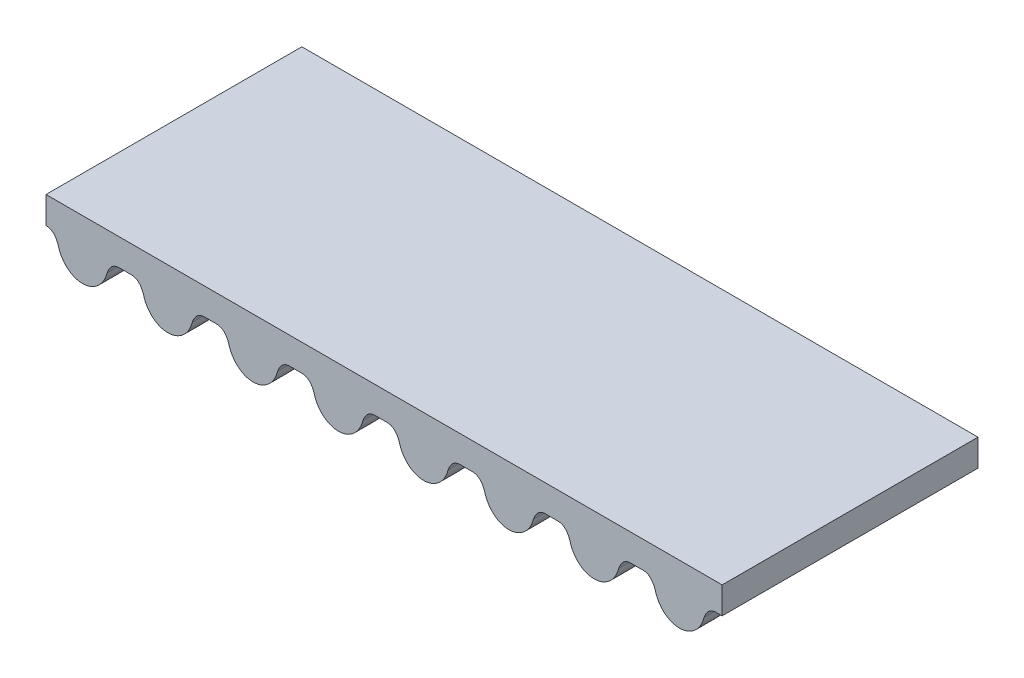
SolidWorks part; units mm, degrees
ref_plane "Front Plane" through (0, 0, 0) normal (0, 0, 1) x (1, 0, 0)
ref_plane "Top Plane" through (0, 0, 0) normal (0, 1, 0) x (1, 0, 0)
ref_plane "Right Plane" through (0, 0, 0) normal (1, 0, 0) x (0, 0, -1)
sketch "Sketch1" plane through (0, 0, 0) normal (0, 0, 1) x (1, 0, 0)
  line L0 (0, 0.75) -> (0, 0) construction
  line L1 (0.8572, 0) -> (0, 0) construction
  line L2 (0, 0.75) -> (0, 1.3798)
  line L12 (3.8572, 1.3798) -> (0, 1.3798)
  line L15 (1.7144, 0.75) -> (1.8572, 0.75)
  line L16 (1.8572, 0.75) -> (2, 0.75)
  line L17 (3.7144, 0.75) -> (3.8572, 0.75)
  line L18 (3.8572, 0.75) -> (4, 0.75)
  line L19 (5.7144, 0.75) -> (5.8572, 0.75)
  line L20 (5.8572, 0.75) -> (6, 0.75)
  line L21 (7.7144, 0.75) -> (7.8572, 0.75)
  line L22 (7.8572, 0.75) -> (8, 0.75)
  line L23 (9.7144, 0.75) -> (9.8572, 0.75)
  line L24 (9.8572, 0.75) -> (10, 0.75)
  line L25 (11.7144, 0.75) -> (11.8572, 0.75)
  line L26 (11.8572, 0.75) -> (12, 0.75)
  line L27 (13.7144, 0.75) -> (13.8572, 0.75)
  line L28 (13.8572, 0.75) -> (14, 0.75)
  line L29 (15.7144, 0.75) -> (15.8572, 0.75)
  line L30 (15.8572, 0.75) -> (15.8572, 1.3798)
  line L31 (15.8572, 1.3798) -> (11.8572, 1.3798)
  line L32 (11.8572, 1.3798) -> (7.8572, 1.3798)
  line L33 (7.8572, 1.3798) -> (3.8572, 1.3798)
  spline S16 degree 2 poles (0, 0.75) (0.1946, 0.75) (0.2844, 0.4991) knots 0.054545 0.054545 0.054545 0.072727 0.072727 0.072727
  spline S17 degree 3 poles (0.2844, 0.4991) (0.355, 0.2112) (0.5844, 0) (0.8572, 0) knots 0.072727 0.072727 0.072727 0.072727 0.090909 0.090909 0.090909 0.090909
  spline S18 degree 3 poles (0.8572, 0) (1.13, 0) (1.3594, 0.2112) (1.43, 0.4991) knots 0.090909 0.090909 0.090909 0.090909 0.109091 0.109091 0.109091 0.109091
  spline S19 degree 2 poles (1.43, 0.4991) (1.5198, 0.75) (1.7144, 0.75) knots 0.109091 0.109091 0.109091 0.127273 0.127273 0.127273
  spline S20 degree 2 poles (2, 0.75) (2.1946, 0.75) (2.2844, 0.4991) knots 0.163636 0.163636 0.163636 0.181818 0.181818 0.181818
  spline S21 degree 3 poles (2.2844, 0.4991) (2.355, 0.2112) (2.5844, 0) (2.8572, 0) knots 0.181818 0.181818 0.181818 0.181818 0.2 0.2 0.2 0.2
  spline S22 degree 3 poles (2.8572, 0) (3.13, 0) (3.3594, 0.2112) (3.43, 0.4991) knots 0.2 0.2 0.2 0.2 0.218182 0.218182 0.218182 0.218182
  spline S23 degree 2 poles (3.43, 0.4991) (3.5198, 0.75) (3.7144, 0.75) knots 0.218182 0.218182 0.218182 0.236364 0.236364 0.236364
  spline S24 degree 2 poles (4, 0.75) (4.1946, 0.75) (4.2844, 0.4991) knots 0.272727 0.272727 0.272727 0.290909 0.290909 0.290909
  spline S25 degree 3 poles (4.2844, 0.4991) (4.355, 0.2112) (4.5844, 0) (4.8572, 0) knots 0.290909 0.290909 0.290909 0.290909 0.309091 0.309091 0.309091 0.309091
  spline S26 degree 3 poles (4.8572, 0) (5.13, 0) (5.3594, 0.2112) (5.43, 0.4991) knots 0.309091 0.309091 0.309091 0.309091 0.327273 0.327273 0.327273 0.327273
  spline S27 degree 2 poles (5.43, 0.4991) (5.5198, 0.75) (5.7144, 0.75) knots 0.327273 0.327273 0.327273 0.345455 0.345455 0.345455
  spline S28 degree 2 poles (6, 0.75) (6.1946, 0.75) (6.2844, 0.4991) knots 0.381818 0.381818 0.381818 0.4 0.4 0.4
  spline S29 degree 3 poles (6.2844, 0.4991) (6.355, 0.2112) (6.5844, 0) (6.8572, 0) knots 0.4 0.4 0.4 0.4 0.418182 0.418182 0.418182 0.418182
  spline S30 degree 3 poles (6.8572, 0) (7.13, 0) (7.3594, 0.2112) (7.43, 0.4991) knots 0.418182 0.418182 0.418182 0.418182 0.436364 0.436364 0.436364 0.436364
  spline S31 degree 2 poles (7.43, 0.4991) (7.5198, 0.75) (7.7144, 0.75) knots 0.436364 0.436364 0.436364 0.454545 0.454545 0.454545
  spline S32 degree 2 poles (8, 0.75) (8.1946, 0.75) (8.2844, 0.4991) knots 0.490909 0.490909 0.490909 0.509091 0.509091 0.509091
  spline S33 degree 3 poles (8.2844, 0.4991) (8.355, 0.2112) (8.5844, 0) (8.8572, 0) knots 0.509091 0.509091 0.509091 0.509091 0.527273 0.527273 0.527273 0.527273
  spline S34 degree 3 poles (8.8572, 0) (9.13, 0) (9.3594, 0.2112) (9.43, 0.4991) knots 0.527273 0.527273 0.527273 0.527273 0.545455 0.545455 0.545455 0.545455
  spline S35 degree 2 poles (9.43, 0.4991) (9.5198, 0.75) (9.7144, 0.75) knots 0.545455 0.545455 0.545455 0.563636 0.563636 0.563636
  spline S36 degree 2 poles (10, 0.75) (10.1946, 0.75) (10.2844, 0.4991) knots 0.6 0.6 0.6 0.618182 0.618182 0.618182
  spline S37 degree 3 poles (10.2844, 0.4991) (10.355, 0.2112) (10.5844, 0) (10.8572, 0) knots 0.618182 0.618182 0.618182 0.618182 0.636364 0.636364 0.636364 0.636364
  spline S38 degree 3 poles (10.8572, 0) (11.13, 0) (11.3594, 0.2112) (11.43, 0.4991) knots 0.636364 0.636364 0.636364 0.636364 0.654545 0.654545 0.654545 0.654545
  spline S39 degree 2 poles (11.43, 0.4991) (11.5198, 0.75) (11.7144, 0.75) knots 0.654545 0.654545 0.654545 0.672727 0.672727 0.672727
  spline S40 degree 2 poles (12, 0.75) (12.1946, 0.75) (12.2844, 0.4991) knots 0.709091 0.709091 0.709091 0.727273 0.727273 0.727273
  spline S41 degree 3 poles (12.2844, 0.4991) (12.355, 0.2112) (12.5844, 0) (12.8572, 0) knots 0.727273 0.727273 0.727273 0.727273 0.745455 0.745455 0.745455 0.745455
  spline S42 degree 3 poles (12.8572, 0) (13.13, 0) (13.3594, 0.2112) (13.43, 0.4991) knots 0.745455 0.745455 0.745455 0.745455 0.763636 0.763636 0.763636 0.763636
  spline S43 degree 2 poles (13.43, 0.4991) (13.5198, 0.75) (13.7144, 0.75) knots 0.763636 0.763636 0.763636 0.781818 0.781818 0.781818
  spline S44 degree 2 poles (14, 0.75) (14.1946, 0.75) (14.2844, 0.4991) knots 0.818182 0.818182 0.818182 0.836364 0.836364 0.836364
  spline S45 degree 3 poles (14.2844, 0.4991) (14.355, 0.2112) (14.5844, 0) (14.8572, 0) knots 0.836364 0.836364 0.836364 0.836364 0.854545 0.854545 0.854545 0.854545
  spline S46 degree 3 poles (14.8572, 0) (15.13, 0) (15.3594, 0.2112) (15.43, 0.4991) knots 0.854545 0.854545 0.854545 0.854545 0.872727 0.872727 0.872727 0.872727
  spline S47 degree 2 poles (15.43, 0.4991) (15.5198, 0.75) (15.7144, 0.75) knots 0.872727 0.872727 0.872727 0.890909 0.890909 0.890909
extrude "Boss-Extrude1" add sketch "Sketch1" along normal blind 3 and the other way blind 3
